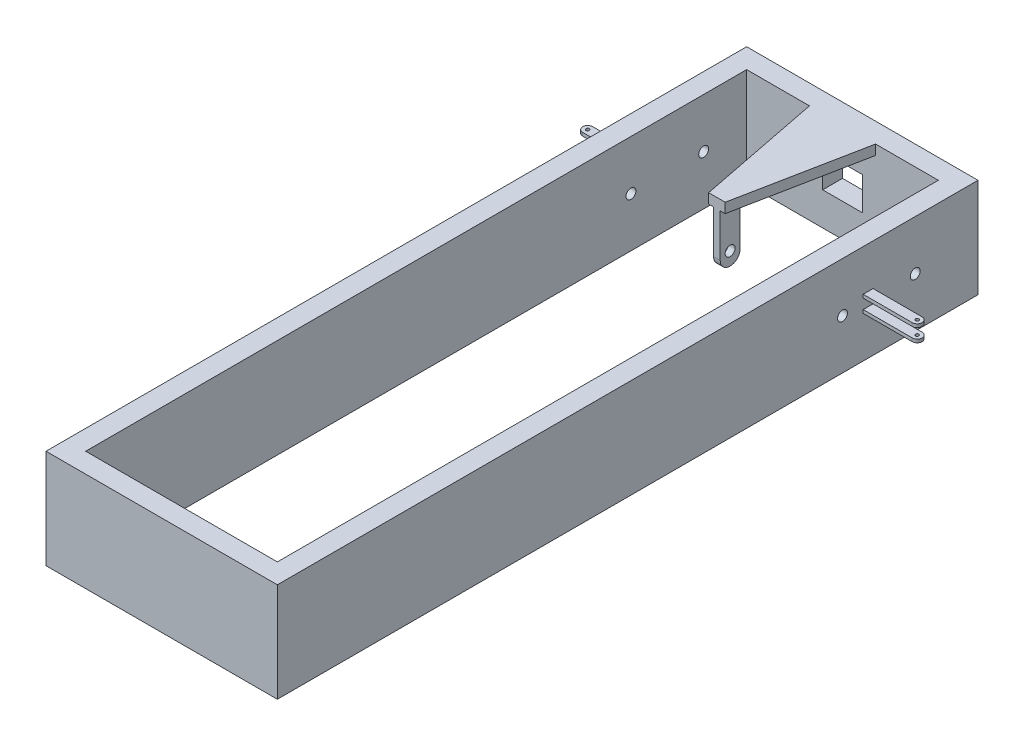
SolidWorks part; units mm, degrees
ref_plane "Front Plane" through (0, 0, 0) normal (0, 0, 1) x (1, 0, 0)
ref_plane "Top Plane" through (0, 0, 0) normal (0, 1, 0) x (1, 0, 0)
ref_plane "Right Plane" through (0, 0, 0) normal (1, 0, 0) x (0, 0, -1)
sketch "Sketch1" plane through (0, 0, 0) normal (0, 1, 0) x (1, 0, 0)
  line L1 (-29, 100) -> (29, 100)
  line L2 (-29, 100) -> (-29, -100)
  line L3 (-29, -100) -> (29, -100)
  line L4 (29, 100) -> (29, -100)
  line L5 (-29, 100) -> (29, -100) construction
  line L6 (-29, -100) -> (29, 100) construction
  line L7 (-35, 106) -> (35, 106)
  line L8 (-35, 106) -> (-35, -106)
  line L9 (-35, -106) -> (35, -106)
  line L10 (35, 106) -> (35, -106)
  line L11 (-35, 106) -> (35, -106) construction
  line L12 (-35, -106) -> (35, 106) construction
  point P0 (0, 0)
  point P6 (0, 0)
  dimension "D1" = 58
  dimension "D2" = 6
  dimension "D3" = 6
  dimension "D4" = 200
extrude "Boss-Extrude1" add sketch "Sketch1" along normal blind 30
ref_plane "Plane1" through (0, 0, -62) normal (0, 0, 1) x (1, 0, 0)
sketch "Sketch7" plane through (0, 0, -100) normal (0, 0, 1) x (1, 0, 0)
  line L0 (-35, 30) -> (35, 30) construction
  line L1 (-10, 30) -> (10, 30)
  line L2 (-10, 30) -> (-10, 27)
  line L3 (-10, 27) -> (10, 27)
  line L4 (10, 30) -> (10, 27)
  line L5 (-35, 30) -> (-35, 0) construction
  dimension "D1" = 3
  dimension "D2" = 20
  dimension "D3" = 25
sketch "Sketch8" plane through (0, 0, -62) normal (0, 0, 1) x (1, 0, 0)
  line L0 (-10, 30) -> (10, 30) construction
  line L1 (-2.5, 30) -> (2.5, 30)
  line L2 (-2.5, 30) -> (-2.5, 27)
  line L3 (-2.5, 27) -> (2.5, 27)
  line L4 (2.5, 30) -> (2.5, 27)
  line L5 (-10, 27) -> (10, 27) construction
  line L6 (10, 30) -> (10, 27) construction
  dimension "D1" = 5
  dimension "D2" = 7.5
sketch "Sketch9" plane through (0, 30, 0) normal (0, 1, 0) x (1, 0, 0)
  line L0 (10, 100) -> (2.5, 62)
  line L1 (-10, 100) -> (10, 100) construction
  line L2 (-2.5, 62) -> (2.5, 62) construction
  line L3 (-16.5058, 62) -> (16.5058, 62) construction
  line L4 (-10, 100) -> (-2.5, 62)
loft "Loft3" add profiles "Sketch7", "Sketch8" connector at (-10, 27, -100) connector at (-2.5, 27, -62)
sketch "Sketch10" plane through (0, 27, 0) normal (0, -1, 0) x (1, 0, 0)
  line L0 (-10, -100) -> (10, -100) construction
  line L1 (-1, -62) -> (1, -62)
  line L2 (-1, -62) -> (-1, -68)
  line L3 (-1, -68) -> (1, -68)
  line L4 (1, -62) -> (1, -68)
  line L6 (-2.5, -62) -> (2.5, -62) construction
  point P5 (1, -65)
  point P10 (0, -62)
  point P11 (0, -62)
  point P12 (-2.5, -62)
  point P13 (-1.8823, -62.6181)
  dimension "D1" = 2
  dimension "D2" = 35
  dimension "D3" = 0
  dimension "D4" = 0
extrude "Boss-Extrude3" add sketch "Sketch10" along normal blind 16
fillet "Fillet2" radius 3 2 edges at (0, 11, -68) (0, 11, -62)
sketch "Sketch2" plane through (35, 0, 0) normal (1, 0, 0) x (0, 0, -1)
  line L0 (106, 30) -> (106, 0) construction
  line L1 (-106, 30) -> (106, 30) construction
  circle A0 centre (65, 15) radius 1.5
  circle A1 centre (87, 15) radius 1.5
  dimension "D2" = 15
  dimension "D3" = 3
  dimension "D5" = 3
  dimension "D1" = 19
  dimension "D4" = 22
extrude "Cut-Extrude1" cut sketch "Sketch2" against normal through all
sketch "Sketch3" plane through (0, 0, -106) normal (0, 0, -1) x (-1, 0, 0)
  line L0 (35, 30) -> (35, 0) construction
  line L1 (-6, 20) -> (6, 20)
  line L2 (-6, 20) -> (-6, 10)
  line L3 (-6, 10) -> (6, 10)
  line L4 (6, 20) -> (6, 10)
  line L5 (-6, 20) -> (6, 10) construction
  line L6 (-6, 10) -> (6, 20) construction
  line L8 (-35, 0) -> (35, 0) construction
  point P0 (0, 15)
  dimension "D1" = 10
  dimension "D2" = 12
  dimension "D3" = 29
  dimension "D4" = 10
extrude "Cut-Extrude2" cut sketch "Sketch3" against normal up to next
sketch "Sketch4" plane through (35, 0, 0) normal (1, 0, 0) x (0, 0, -1)
  line L17 (65, 15) -> (65, 11.0458) construction
  line L18 (72.25, 15) -> (73.25, 15) construction
  line L19 (74.25, 12.5) -> (74.25, 13.5)
  line L20 (74.25, 12.5) -> (71.25, 12.5)
  line L21 (71.25, 12.5) -> (71.25, 13.5)
  line L22 (74.25, 13.5) -> (71.25, 13.5)
  line L23 (71.25, 17.5) -> (71.25, 16.5)
  line L24 (74.25, 16.5) -> (71.25, 16.5)
  line L25 (74.25, 17.5) -> (74.25, 16.5)
  line L26 (74.25, 17.5) -> (71.25, 17.5)
extrude "Boss-Extrude2" add sketch "Sketch4" along normal blind 16.35
fillet "Fillet1" radius 1.5 4 edges at (51.35, 13, -74.25) (51.35, 13, -71.25) (51.35, 17, -71.25) (51.35, 17, -74.25)
sketch "Sketch6" plane through (0, 17.5, 0) normal (0, 1, 0) x (1, 0, 0)
  circle A0 centre (49.85, 72.75) radius 0.5
extrude "Cut-Extrude4" cut sketch "Sketch6" against normal through all
mirror "Mirror2" about plane through (0, 0, 0) normal (1, 0, 0) of "Boss-Extrude2", "Fillet1", "Cut-Extrude4"
